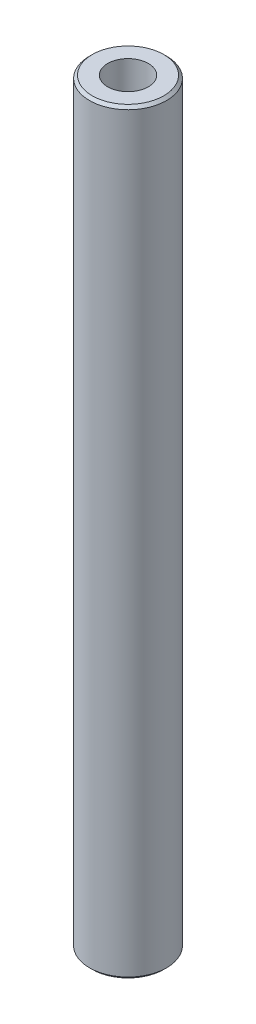
SolidWorks part; units mm, degrees
ref_plane "Front Plane" through (0, 0, 0) normal (0, 0, 1) x (1, 0, 0)
ref_plane "Top Plane" through (0, 0, 0) normal (0, 1, 0) x (1, 0, 0)
ref_plane "Right Plane" through (0, 0, 0) normal (1, 0, 0) x (0, 0, -1)
sketch "Sketch1" plane through (0, 0, 0) normal (0, 1, 0) x (1, 0, 0)
  circle A0 centre (0, 0) radius 5
  dimension "SHAFT_OD" = 10
extrude "Boss-Extrude1" add sketch "Sketch1" along normal blind 98.2329
sketch "Sketch2" plane through (0, 0, 0) normal (0, 1, 0) x (1, 0, 0)
  circle A0 centre (0, 0) radius 2.6361
  dimension "BORE_D" = 5.2723
extrude "Cut-Extrude1" cut sketch "Sketch2" along normal through all
chamfer "Chamfer1" distance 0.3579 angle 45 2 edges at (0, 98.2329, 5) (0, 0, 5)
